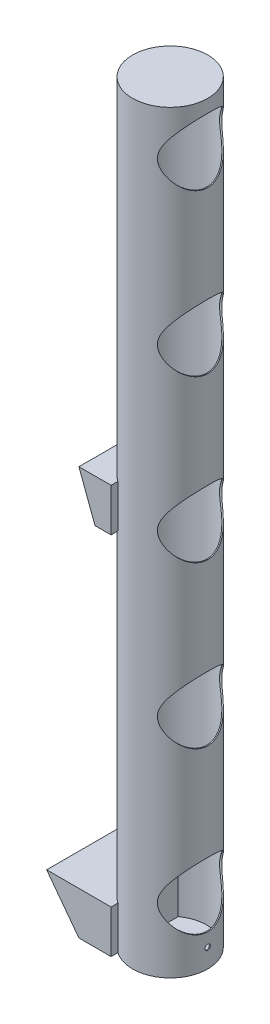
SolidWorks part; units mm, degrees
ref_plane "Спереди" through (0, 0, 0) normal (0, 0, 1) x (1, 0, 0)
ref_plane "Сверху" through (0, 0, 0) normal (0, 1, 0) x (1, 0, 0)
ref_plane "Справа" through (0, 0, 0) normal (1, 0, 0) x (0, 0, -1)
sketch "Эскиз2" plane through (0, 0, 0) normal (0, 1, 0) x (1, 0, 0)
  circle A0 centre (0, 0) radius 35
  circle A1 centre (0, 0) radius 34
  dimension "D1" = 70
  dimension "D2" = 68
extrude "Бобышка-Вытянуть1" add sketch "Эскиз2" along normal blind 700
sketch "Эскиз3" plane through (0, 0, 0) normal (0, -1, 0) x (1, 0, 0)
  circle A0 centre (0, 0) radius 35
extrude "Бобышка-Вытянуть2" add sketch "Эскиз3" along normal blind 1
sketch "Эскиз4" plane through (0, 700, 0) normal (0, 1, 0) x (1, 0, 0)
  circle A0 centre (0, 0) radius 35
extrude "Бобышка-Вытянуть3" add sketch "Эскиз4" along normal blind 1
sketch "Эскиз5" plane through (0, 0, 0) normal (1, 0, 0) x (0, 0, -1)
  line L0 (-35, -1) -> (35, -1) construction
  circle A0 centre (0, 16.5) radius 2.5
  circle A1 centre (0, 59) radius 30
  circle A2 centre (0, 209) radius 30
  circle A3 centre (0, 359) radius 30
  circle A4 centre (0, 509) radius 30
  circle A5 centre (0, 659) radius 30
  point P3 (0, 0)
  dimension "D1" = 5
  dimension "D2" = 15
  dimension "D3" = 60
  dimension "D4" = 60
  dimension "D6" = 150
  dimension "D5" = 5
extrude "Вырез-Вытянуть1" cut sketch "Эскиз5" along normal through all
sketch "Эскиз6" plane through (0, 0, 0) normal (1, 0, 0) x (0, 0, -1)
  line L0 (35, 701) -> (-35, 701) construction
  circle A0 centre (0, 686) radius 10
  point P4 (1.9439, 686)
  point P5 (0, 0)
  dimension "D1" = 20
  dimension "D2" = 15
extrude "Вырез-Вытянуть2" cut sketch "Эскиз6" against normal through all
sketch "Эскиз7" plane through (0, 0, 0) normal (1, 0, 0) x (0, 0, -1)
  line L0 (-35, -1) -> (35, -1) construction
  line L1 (-35, 39) -> (35, 39)
  line L2 (-35, 39) -> (-35, -1)
  line L3 (-35, -1) -> (35, -1)
  line L4 (35, 39) -> (35, -1)
  line L5 (-35, 701) -> (-35, -1) construction
  line L10 (35, -1) -> (35, 701) construction
  dimension "D1" = 0
  dimension "D2" = 0
  dimension "D3" = 40
extrude "Бобышка-Вытянуть4" add sketch "Эскиз7" against normal blind 60 from offset 20 offset against normal yes
sketch "Эскиз8" plane through (0, 0, 0) normal (1, 0, 0) x (0, 0, -1)
  line L0 (35, -1) -> (35, 701) construction
  line L1 (-35, 379) -> (35, 379)
  line L2 (-35, 379) -> (-35, 339)
  line L3 (-35, 339) -> (35, 339)
  line L4 (35, 379) -> (35, 339)
  line L5 (-35, 701) -> (-35, -1) construction
  line L6 (-35, -1) -> (35, -1) construction
  dimension "D1" = 40
  dimension "D2" = 0
  dimension "D3" = 0
  dimension "D4" = 340
extrude "Бобышка-Вытянуть5" add sketch "Эскиз8" along normal blind 30 from offset 50 offset against normal yes
sketch "Эскиз9" plane through (0, 0, 0) normal (0, 0, 1) x (1, 0, 0)
  line L0 (-50, -1) -> (-80, 39)
  line L1 (-80, 39) -> (-80, -1)
  line L2 (-80, -1) -> (-50, -1)
  line L3 (-35, 339) -> (-50, 379)
  line L4 (-50, 379) -> (-50, 339)
  line L5 (-50, 339) -> (-35, 339)
  line L6 (-20, 339) -> (-50, 339) construction
  line L7 (-80, -1) -> (-20, -1) construction
  point P6 (0, 0)
  point P8 (0, 0)
  point P11 (-35, 339)
  point P12 (-80, 39)
  point P14 (-80, -1)
  point P16 (-50, -1)
extrude "Вырез-Вытянуть3" cut sketch "Эскиз9" against normal through all both and the other way through all
